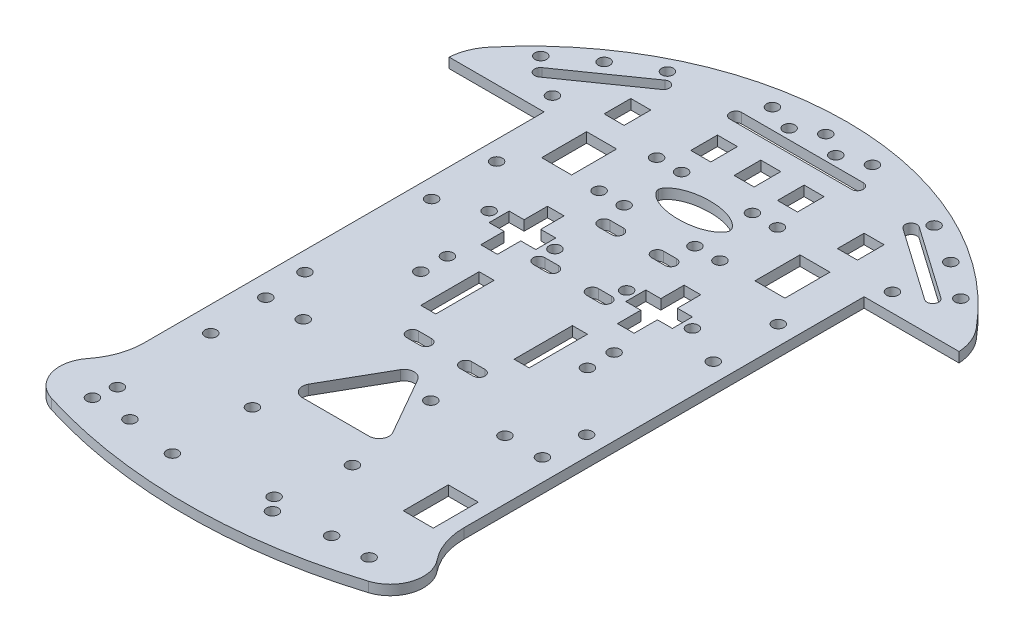
SolidWorks part; units mm, degrees
ref_plane "Front Plane" through (0, 0, 0) normal (0, 0, 1) x (1, 0, 0)
ref_plane "Top Plane" through (0, 0, 0) normal (0, 1, 0) x (1, 0, 0)
ref_plane "Right Plane" through (0, 0, 0) normal (1, 0, 0) x (0, 0, -1)
ref_plane "Plane4" through (0, -1.5, 0) normal (0, -1, 0) x (1, 0, 0)
sketch "Sketch1" plane through (0, -1.5, 0) normal (0, -1, 0) x (1, 0, 0)
  line L0 (6, 21.75) -> (10, 21.75)
  line L1 (10, 18.25) -> (6, 18.25)
  line L2 (-10, 41.25) -> (-6, 41.25)
  line L3 (-6, 37.75) -> (-10, 37.75)
  line L4 (6, 79.25) -> (10, 79.25)
  line L5 (10, 75.75) -> (6, 75.75)
  line L6 (-10, 110.5) -> (10, 110.5)
  line L7 (12.6047, 106.0116) -> (2.6047, 88.5116)
  line L8 (-2.6047, 88.5116) -> (-12.6047, 106.0116)
  line L9 (-57.85, -8.3165) -> (-36.1425, -23.5163)
  line L10 (-38.15, -26.3833) -> (-59.8575, -11.1835)
  line L11 (23, 44) -> (23, 37)
  line L12 (23, 37) -> (27.5, 37)
  line L13 (27.5, 37) -> (27.5, 31)
  line L14 (27.5, 31) -> (23, 31)
  line L15 (23, 31) -> (23, 24)
  line L16 (23, 24) -> (18, 24)
  line L17 (18, 24) -> (18, 31)
  line L18 (18, 31) -> (13.5, 31)
  line L19 (13.5, 31) -> (13.5, 37)
  line L20 (13.5, 37) -> (18, 37)
  line L21 (18, 37) -> (18, 44)
  line L22 (18, 44) -> (23, 44)
  line L23 (16.25, 51.25) -> (11.75, 51.25)
  line L24 (11.75, 51.25) -> (11.75, 68.75)
  line L25 (11.75, 68.75) -> (16.25, 68.75)
  line L26 (16.25, 68.75) -> (16.25, 51.25)
  line L27 (43.5, 111.25) -> (34.5, 111.25)
  line L28 (34.5, 111.25) -> (34.5, 124.75)
  line L29 (34.5, 124.75) -> (43.5, 124.75)
  line L30 (43.5, 124.75) -> (43.5, 111.25)
  line L31 (-27.5, -1.25) -> (-36.5, -1.25)
  line L32 (-36.5, -1.25) -> (-36.5, 12.25)
  line L33 (-36.5, 12.25) -> (-27.5, 12.25)
  line L34 (-27.5, 12.25) -> (-27.5, -1.25)
  line L35 (16, -20) -> (10, -20)
  line L36 (10, -20) -> (10, -12)
  line L37 (10, -12) -> (16, -12)
  line L38 (16, -12) -> (16, -20)
  line L39 (37.5, -16.5) -> (31.5, -16.5)
  line L40 (31.5, -16.5) -> (31.5, -8.5)
  line L41 (31.5, -8.5) -> (37.5, -8.5)
  line L42 (37.5, -8.5) -> (37.5, -16.5)
  line L43 (-48, 0) -> (-76.5, 0)
  line L44 (76.5, 0) -> (48, 0)
  line L45 (48, 0) -> (48, 120)
  line L46 (-48, 120) -> (-48, 0)
  line L47 (-32.5, -16.5) -> (-38.5, -16.5)
  line L48 (-38.5, -16.5) -> (-38.5, -8.5)
  line L49 (-38.5, -8.5) -> (-32.5, -8.5)
  line L50 (-32.5, -8.5) -> (-32.5, -16.5)
  line L51 (-10, -20) -> (-16, -20)
  line L52 (-16, -20) -> (-16, -12)
  line L53 (-16, -12) -> (-10, -12)
  line L54 (-10, -12) -> (-10, -20)
  line L55 (3, -20) -> (-3, -20)
  line L56 (-3, -20) -> (-3, -12)
  line L57 (-3, -12) -> (3, -12)
  line L58 (3, -12) -> (3, -20)
  line L59 (36.5, -1.25) -> (27.5, -1.25)
  line L60 (27.5, -1.25) -> (27.5, 12.25)
  line L61 (27.5, 12.25) -> (36.5, 12.25)
  line L62 (36.5, 12.25) -> (36.5, -1.25)
  line L63 (-11.75, 51.25) -> (-16.25, 51.25)
  line L64 (-16.25, 51.25) -> (-16.25, 68.75)
  line L65 (-16.25, 68.75) -> (-11.75, 68.75)
  line L66 (-11.75, 68.75) -> (-11.75, 51.25)
  line L67 (-18, 44) -> (-18, 37)
  line L68 (-18, 37) -> (-13.5, 37)
  line L69 (-13.5, 37) -> (-13.5, 31)
  line L70 (-13.5, 31) -> (-18, 31)
  line L71 (-18, 31) -> (-18, 24)
  line L72 (-18, 24) -> (-23, 24)
  line L73 (-23, 24) -> (-23, 31)
  line L74 (-23, 31) -> (-27.5, 31)
  line L75 (-27.5, 31) -> (-27.5, 37)
  line L76 (-27.5, 37) -> (-23, 37)
  line L77 (-23, 37) -> (-23, 44)
  line L78 (-23, 44) -> (-18, 44)
  line L79 (-18.25, -26) -> (18.25, -26)
  line L80 (18.25, -29.5) -> (-18.25, -29.5)
  line L81 (59.8575, -11.1835) -> (38.15, -26.3833)
  line L82 (36.1425, -23.5163) -> (57.85, -8.3165)
  line L83 (-10, 79.25) -> (-6, 79.25)
  line L84 (-6, 75.75) -> (-10, 75.75)
  line L85 (6, 41.25) -> (10, 41.25)
  line L86 (10, 37.75) -> (6, 37.75)
  line L87 (-10, 21.75) -> (-6, 21.75)
  line L88 (-6, 18.25) -> (-10, 18.25)
  arc A0 (10, 21.75) -> (10, 18.25) centre (10, 20) cw
  arc A1 (6, 18.25) -> (6, 21.75) centre (6, 20) cw
  arc A2 (-6, 41.25) -> (-6, 37.75) centre (-6, 39.5) cw
  arc A3 (-10, 37.75) -> (-10, 41.25) centre (-10, 39.5) cw
  arc A4 (10, 79.25) -> (10, 75.75) centre (10, 77.5) cw
  arc A5 (6, 75.75) -> (6, 79.25) centre (6, 77.5) cw
  arc A6 (10, 110.5) -> (12.6047, 106.0116) centre (10, 107.5) cw
  arc A7 (2.6047, 88.5116) -> (-2.6047, 88.5116) centre (0, 90) cw
  arc A8 (-12.6047, 106.0116) -> (-10, 110.5) centre (-10, 107.5) cw
  arc A9 (-36.1425, -23.5163) -> (-38.15, -26.3833) centre (-37.1462, -24.9498) cw
  arc A10 (-59.8575, -11.1835) -> (-57.85, -8.3165) centre (-58.8538, -9.75) cw
  arc A11 (-76.5, 0) -> (-73.0709, -8.5857) centre (-61.5334, 1) ccw
  arc A12 (-73.0709, -8.5857) -> (73.0709, -8.5857) centre (0, 52.1238) ccw
  arc A13 (73.0709, -8.5857) -> (76.5, 0) centre (61.5334, 1) ccw
  arc A14 (48, 120) -> (52.3755, 132.485) centre (68, 120) cw
  arc A15 (52.3755, 132.485) -> (47.5341, 148.276) centre (44.5633, 138.7275) ccw
  arc A16 (47.5341, 148.276) -> (-47.5341, 148.276) centre (0, -4.5) ccw
  arc A17 (-47.5341, 148.276) -> (-52.3755, 132.485) centre (-44.5633, 138.7275) ccw
  arc A18 (-52.3755, 132.485) -> (-48, 120) centre (-68, 120) cw
  arc A19 (18.25, -26) -> (18.25, -29.5) centre (18.25, -27.75) cw
  arc A20 (-18.25, -29.5) -> (-18.25, -26) centre (-18.25, -27.75) cw
  arc A21 (38.15, -26.3833) -> (36.1425, -23.5163) centre (37.1462, -24.9498) cw
  arc A22 (57.85, -8.3165) -> (59.8575, -11.1835) centre (58.8538, -9.75) cw
  arc A23 (-6, 79.25) -> (-6, 75.75) centre (-6, 77.5) cw
  arc A24 (-10, 75.75) -> (-10, 79.25) centre (-10, 77.5) cw
  arc A25 (10, 41.25) -> (10, 37.75) centre (10, 39.5) cw
  arc A26 (6, 37.75) -> (6, 41.25) centre (6, 39.5) cw
  arc A27 (-6, 21.75) -> (-6, 18.25) centre (-6, 20) cw
  arc A28 (-10, 18.25) -> (-10, 21.75) centre (-10, 20) cw
  circle A29 centre (-7, -32.5) radius 1.75
  circle A30 centre (0, -36.5) radius 1.75
  circle A31 centre (7, -32.5) radius 1.75
  circle A32 centre (15, -35.5) radius 1.75
  circle A33 centre (-15, -35.5) radius 1.75
  circle A34 centre (-40, -29) radius 1.75
  circle A35 centre (-52, -22) radius 1.75
  circle A36 centre (-63, -14) radius 1.75
  circle A37 centre (63, -14) radius 1.75
  circle A38 centre (52, -22) radius 1.75
  circle A39 centre (40, -29) radius 1.75
  circle A40 centre (-19.25, -5) radius 1.75
  circle A41 centre (-11.75, -5) radius 1.75
  circle A42 centre (-11.75, 12.25) radius 1.75
  circle A43 centre (-19.25, 12.25) radius 1.75
  circle A44 centre (9.5, 12.25) radius 1.75
  circle A45 centre (17, 12.25) radius 1.75
  circle A46 centre (17, -5) radius 1.75
  circle A47 centre (9.5, -5) radius 1.75
  circle A48 centre (-51, -5.5) radius 1.75
  circle A49 centre (-42.25, 20) radius 1.75
  circle A50 centre (42.25, 20) radius 1.75
  circle A51 centre (51, -5.5) radius 1.75
  circle A52 centre (-10.75, 34) radius 1.75
  circle A53 centre (-30.5, 34) radius 1.75
  circle A54 centre (10.75, 34) radius 1.75
  circle A55 centre (30.5, 34) radius 1.75
  circle A56 centre (42.25, 39.5) radius 1.75
  circle A57 centre (25, 52) radius 1.75
  circle A58 centre (25, 60) radius 1.75
  circle A59 centre (-25, 60) radius 1.75
  circle A60 centre (-25, 52) radius 1.75
  circle A61 centre (-42.25, 39.5) radius 1.75
  circle A62 centre (-42.25, 77.4983) radius 1.75
  circle A63 centre (-41.5, 90) radius 1.75
  circle A64 centre (-30.25, 90) radius 1.75
  circle A65 centre (-40.5, 107.5) radius 1.75
  circle A66 centre (-15, 120.5) radius 1.75
  circle A67 centre (-40.5, 135.5) radius 1.75
  circle A68 centre (-41.5, 142) radius 1.75
  circle A69 centre (-30.25, 142) radius 1.75
  circle A70 centre (-15, 144.5) radius 1.75
  circle A71 centre (11.5, 140.5) radius 1.75
  circle A72 centre (15, 144.5) radius 1.75
  circle A73 centre (30.25, 142) radius 1.75
  circle A74 centre (41.5, 142) radius 1.75
  circle A75 centre (15, 120.5) radius 1.75
  circle A76 centre (10, 92) radius 1.75
  circle A77 centre (30.25, 90) radius 1.75
  circle A78 centre (41.5, 90) radius 1.75
  circle A79 centre (42.25, 77.4983) radius 1.75
  spline S0 degree 3 poles (10.75, 3) (10.75, 4.5833) (7.1667, 7.75) (-7.1667, 7.75) (-10.75, 4.5833) (-10.75, 3) knots 0 0 0 0 0.5 0.5 1 1 1 1
  spline S1 degree 3 poles (-10.75, 3) (-10.75, 1.4167) (-7.1667, -1.75) (7.1667, -1.75) (10.75, 1.4167) (10.75, 3) knots 0 0 0 0 0.5 0.5 1 1 1 1
  dimension "D1" = 3.5
  dimension "D2" = 3.5
  dimension "D3" = 3.5
  dimension "D4" = 3.5
  dimension "D5" = 3.5
  dimension "D6" = 3.5
  dimension "D7" = 3.5
  dimension "D8" = 3.5
  dimension "D9" = 3.5
  dimension "D10" = 3.5
  dimension "D11" = 3.5
  dimension "D12" = 3.5
  dimension "D13" = 3.5
  dimension "D14" = 3.5
  dimension "D15" = 3.5
  dimension "D16" = 3.5
  dimension "D17" = 3.5
  dimension "D18" = 3.5
  dimension "D19" = 3.5
  dimension "D20" = 3.5
  dimension "D21" = 3.5
  dimension "D22" = 3.5
  dimension "D23" = 3.5
  dimension "D24" = 3.5
  dimension "D25" = 3.5
  dimension "D26" = 3.5
  dimension "D27" = 3.5
  dimension "D28" = 3.5
  dimension "D29" = 3.5
  dimension "D30" = 3.5
  dimension "D31" = 3.5
  dimension "D32" = 3.5
  dimension "D33" = 3.5
  dimension "D34" = 3.5
  dimension "D35" = 3.5
  dimension "D36" = 3.5
  dimension "D37" = 3.5
  dimension "D38" = 3.5
  dimension "D39" = 3.5
  dimension "D40" = 3.5
  dimension "D41" = 3.5
  dimension "D42" = 3.5
  dimension "D43" = 3.5
  dimension "D44" = 3.5
  dimension "D45" = 3.5
  dimension "D46" = 3.5
  dimension "D47" = 3.5
  dimension "D48" = 3.5
  dimension "D49" = 3.5
  dimension "D50" = 3.5
  dimension "D51" = 3.5
  dimension "D52" = 1.75
  dimension "D53" = 1.75
  dimension "D54" = 1.75
  dimension "D55" = 3
  dimension "D56" = 3
  dimension "D57" = 1.75
  dimension "D58" = 15
  dimension "D59" = 95
  dimension "D60" = 20
  dimension "D61" = 10
  dimension "D62" = 160
  dimension "D63" = 1.75
  dimension "D64" = 1.75
  dimension "D65" = 0.4659
  dimension "D66" = 3.4367
  dimension "D67" = 5.75
  dimension "D68" = 6.5
  dimension "D69" = 7.5
  dimension "D70" = 8
  dimension "D71" = 9.5
  dimension "D72" = 9.85
  dimension "D73" = 10.8538
  dimension "D74" = 11.5
  dimension "D75" = 11.8575
  dimension "D76" = 15.5
  dimension "D77" = 17.5
  dimension "D78" = 17.75
  dimension "D79" = 20.5
  dimension "D80" = 23
  dimension "D81" = 25
  dimension "D82" = 28.75
  dimension "D83" = 29.75
  dimension "D84" = 30
  dimension "D85" = 31.75
  dimension "D86" = 32
  dimension "D87" = 33
  dimension "D88" = 34.5
  dimension "D89" = 35.3953
  dimension "D90" = 36.25
  dimension "D91" = 37.25
  dimension "D92" = 38
  dimension "D93" = 41
  dimension "D94" = 42
  dimension "D95" = 45
  dimension "D96" = 84.1425
  dimension "D97" = 109.5334
  dimension "D98" = 124.5
  dimension "D99" = 51
  dimension "D100" = 54
  dimension "D101" = 55
  dimension "D102" = 57.5
  dimension "D103" = 9.85
  dimension "D104" = 58.75
  dimension "D105" = 59.5
  dimension "D106" = 59.75
  dimension "D107" = 0.5
  dimension "D108" = 61.5
  dimension "D109" = 63
  dimension "D110" = 64
  dimension "D111" = 64.25
  dimension "D112" = 65
  dimension "D113" = 66
  dimension "D114" = 66.25
  dimension "D115" = 71
  dimension "D116" = 73
  dimension "D117" = 75.5
  dimension "D118" = 78.25
  dimension "D119" = 78.5
  dimension "D120" = 79.5
  dimension "D121" = 82.5
  dimension "D122" = 3.1167
  dimension "D123" = 84.5
  dimension "D124" = 20.9143
  dimension "D125" = 85.5
  dimension "D126" = 25
  dimension "D127" = 88
  dimension "D128" = 89.5
  dimension "D129" = 90.25
  dimension "D130" = 91.5
  dimension "D131" = 7.5
  dimension "D132" = 9.5
  dimension "D133" = 13
  dimension "D134" = 99
  dimension "D135" = 100
  dimension "D136" = 15.5
  dimension "D137" = 17.5
  dimension "D138" = 118.0116
  dimension "D141" = 111
  dimension "D142" = 21
  dimension "D144" = 24
  dimension "D145" = 3
  dimension "D146" = 4
  dimension "D147" = 24.5
  dimension "D149" = 28.25
  dimension "D152" = 15
  dimension "D153" = 32.5
  dimension "D154" = 41.75
  dimension "D155" = 49.5
  dimension "D156" = 53.5
  dimension "D157" = 60.5
  dimension "D158" = 63.5
  dimension "D159" = 66.5
  dimension "D160" = 69
  dimension "D161" = 73.5
  dimension "D162" = 80.75
  dimension "D163" = 81.5
  dimension "D165" = 89.5
  dimension "D166" = 98.25
  dimension "D167" = 106.9983
  dimension "D168" = 107
  dimension "D171" = 121.5
  dimension "D175" = 140.75
  dimension "D177" = 150
  dimension "D178" = 154.25
  dimension "D180" = 165
  dimension "D182" = 170
  dimension "D183" = 171.5
  dimension "D184" = 174
  dimension "D186" = 3
  dimension "D187" = 6
  dimension "D188" = 7
extrude "Boss-Extrude1" add sketch "Sketch1" against normal blind 3
